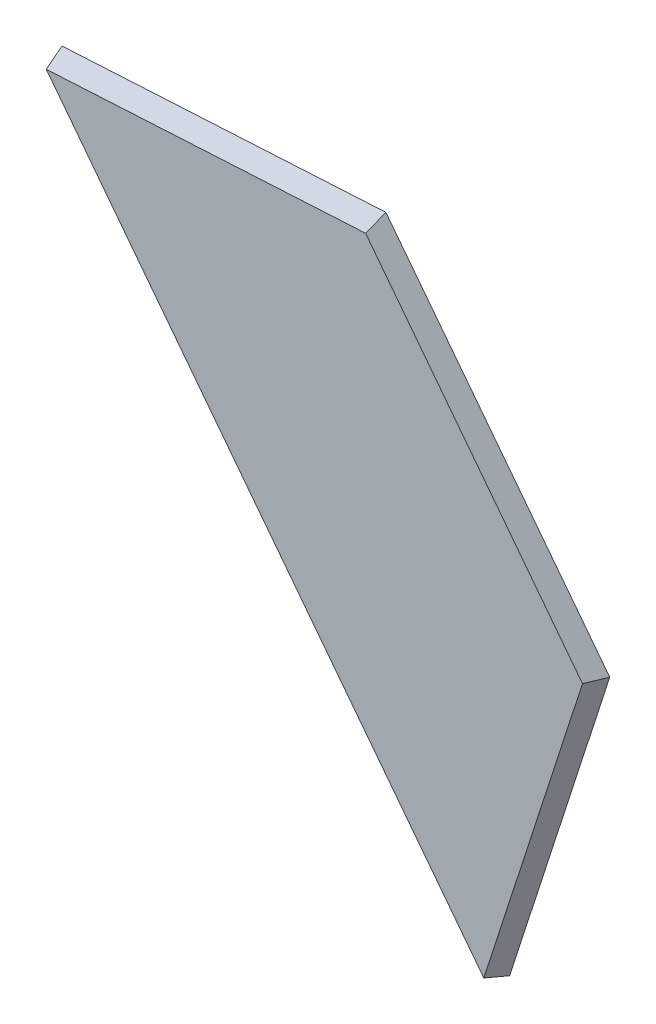
SolidWorks part; units mm, degrees
ref_plane "Спереди" through (0, 0, 0) normal (0, 0, 1) x (1, 0, 0)
ref_plane "Сверху" through (0, 0, 0) normal (0, 1, 0) x (1, 0, 0)
ref_plane "Справа" through (0, 0, 0) normal (1, 0, 0) x (0, 0, -1)
sketch "Эскиз1" plane through (0, 0, 0) normal (0, 0, 1) x (1, 0, 0)
  line L0 (-849.5899, 515.839) -> (787.506, 606.4051)
  line L1 (787.506, 606.4051) -> (281.6156, -953.1975)
  line L2 (281.6156, -953.1975) -> (-849.5899, 515.839)
extrude "Бобышка-Вытянуть1" add sketch "Эскиз1" along normal blind 60
chamfer "Chamfer3" distance 60 angle 11.23 1 edges at (-31.0419, 561.122, 60) first distance on face at (-31.0419, 561.122, 30)
chamfer "Chamfer4" distance 60 angle 11.23 1 edges at (532.5904, -179.4708, 60) first distance on face at (533.5756, -176.4335, 30)
chamfer "Chamfer5" distance 60 angle 9.015 1 edges at (-283.9872, -218.6793, 60) first distance on face at (-283.9872, -218.6793, 30)
sketch "Sketch1" plane through (0, 0, 0) normal (0, 0, -1) x (-1, 0, 0)
  line L1 (-787.506, 606.4051) -> (849.5899, 515.839) construction
  line L2 (-787.506, 606.4051) -> (-534.5608, -173.3962)
  line L3 (-281.6156, -953.1975) -> (-787.506, 606.4051) construction
  line L4 (-534.5608, -173.3962) -> (31.0419, 561.122)
  line L5 (31.0419, 561.122) -> (-787.506, 606.4051)
extrude "Cut-Extrude1" cut sketch "Sketch1" against normal through all
equation "\"D1@Бобышка-Вытянуть1\" = \"THI@Geocorkwithdoor1.0.Assembly\""
equation "\"D2@Chamfer3\" = \"ABchanferAngle@Geocorkwithdoor1.0.Assembly\""
equation "\"D2@Chamfer4\" = \"ABchanferAngle@Geocorkwithdoor1.0.Assembly\""
equation "\"DC1@Chamfer\" = \"THI@Geocorkwithdoor1.0.Assembly\""
equation "\"DC2@Chamfer\" = \"ABchanferAngle@Geocorkwithdoor1.0.Assembly\""
equation "\"DC2@Chamfer\" = \"AAchanferangle@Geocorkwithdoor1.0.Assembly\""
